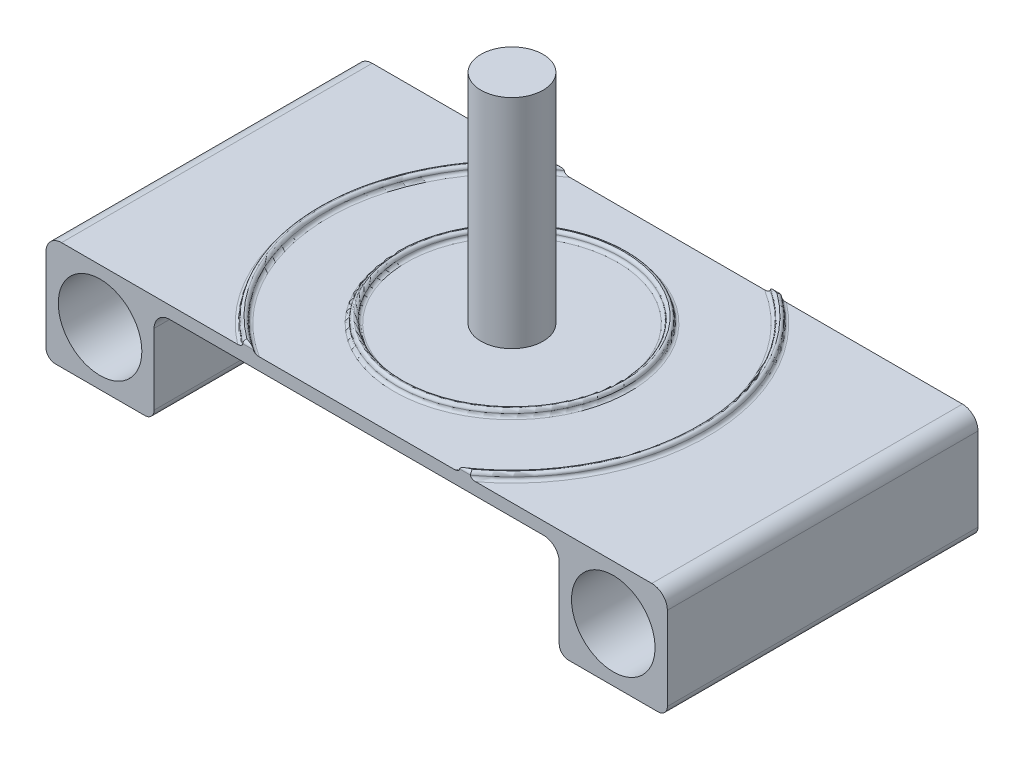
SolidWorks part; units mm, degrees
ref_plane "Front Plane" through (0, 0, 0) normal (0, 0, 1) x (1, 0, 0)
ref_plane "Top Plane" through (0, 0, 0) normal (0, 1, 0) x (1, 0, 0)
ref_plane "Right Plane" through (0, 0, 0) normal (1, 0, 0) x (0, 0, -1)
sketch "Sketch1" plane through (0, 0, 0) normal (0, 0, 1) x (1, 0, 0)
  line L1 (-17.4, 17.4) -> (17.4, 17.4)
  line L2 (-17.4, 17.4) -> (-17.4, -17.4)
  line L3 (-17.4, -17.4) -> (17.4, -17.4)
  line L4 (17.4, 13.4) -> (17.4, -17.4)
  line L5 (-17.4, 17.4) -> (17.4, -17.4) construction
  line L6 (-17.4, -17.4) -> (17.4, 17.4) construction
  line L7 (17.4, 17.4) -> (82.6, 17.4)
  line L9 (17.4, 13.4) -> (82.6, 13.4)
  line L10 (82.6, 17.4) -> (82.6, 13.4)
  circle A0 centre (0, 0) radius 13.45
  point P1 (0, 0)
  dimension "D3" = 26.9
  dimension "D1" = 34.8
  dimension "D2" = 34.8
  dimension "D4" = 65.2
  dimension "D5" = 4
extrude "Boss-Extrude1" add sketch "Sketch1" against normal blind 100
mirror "Mirror1" about plane through (82.6, 17.4, -100) normal (1, 0, 0) of "Boss-Extrude1"
sketch "Sketch2" plane through (0, 17.4, 0) normal (0, 1, 0) x (1, 0, 0)
  line L0 (-17.4, 50) -> (182.6, 50) construction
  line L1 (-17.4, 100) -> (-17.4, 0) construction
  line L2 (182.6, 100) -> (182.6, 0) construction
  circle A0 centre (82.6, 50) radius 10
  dimension "D1" = 20
extrude "Boss-Extrude2" add sketch "Sketch2" along normal blind 70
sketch "Sketch3" plane through (0, 17.4, 0) normal (0, 1, 0) x (1, 0, 0)
  circle A0 centre (82.6, 50) radius 35
  circle A1 centre (82.6, 50) radius 37
  circle A2 centre (82.6, 50) radius 60
  circle A3 centre (82.6, 50) radius 62
  line M3 (-17.4, 0) -> (182.6, 0)
  line M5 (182.6, 100) -> (-17.4, 100)
  dimension "D1" = 70
  dimension "D3" = 120
  dimension "D2" = 2
  dimension "D4" = 2
extrude "Boss-Extrude3" add sketch "Sketch3" along normal blind 2 contours A3 A2 M5 M3 | A1 A0 | A3 A2 M3 M5
fillet "Fillet1" radius 1 24 edges at (49.4338, 18.4, -100) (20.6, 17.4, -50) (45.9394, 18.4, -100) (45.9394, 18.4, 0) (22.6, 19.4, -50) (49.4338, 18.4, 0) (47.6866, 19.4, -100) (20.6, 19.4, -50) (47.6866, 19.4, 0) (22.6, 17.4, -50) (82.6, 17.4, -15) (82.6, 19.4, -15) (82.6, 17.4, -13) (82.6, 19.4, -13) (115.7662, 18.4, 0) (144.6, 17.4, -50) (119.2606, 18.4, 0) (119.2606, 18.4, -100) (142.6, 19.4, -50) (115.7662, 18.4, -100) (117.5134, 19.4, 0) (144.6, 19.4, -50) (117.5134, 19.4, -100) (142.6, 17.4, -50)
fillet "Fillet2" radius 5 4 edges at (-17.4, 17.4, -50) (17.4, 13.4, -50) (147.8, 13.4, -50) (182.6, 17.4, -50)
fillet "Fillet3" radius 3 4 edges at (182.6, -17.4, -50) (147.8, -17.4, -50) (17.4, -17.4, -50) (-17.4, -17.4, -50)
